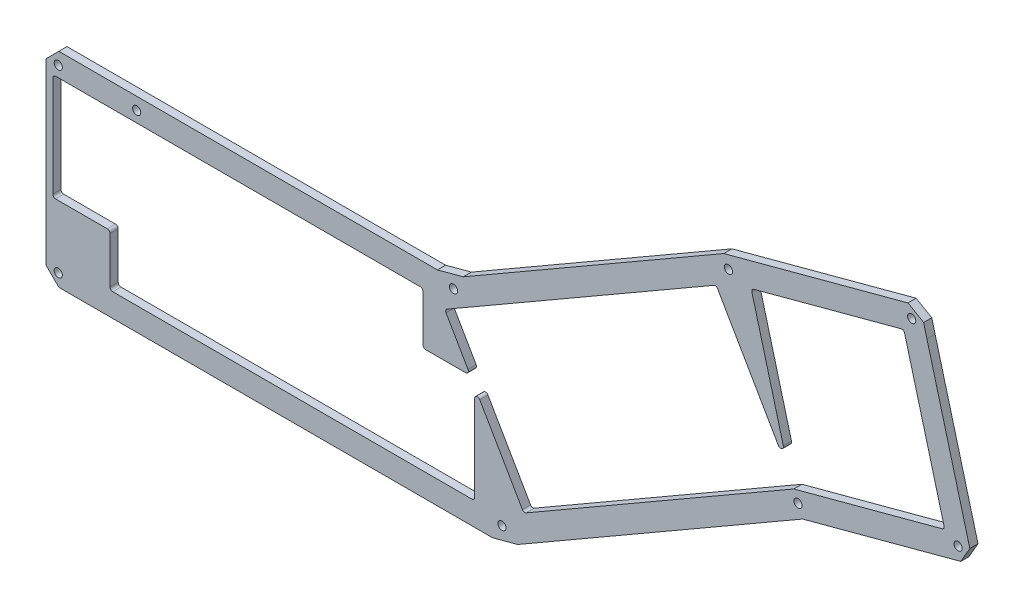
SolidWorks part; units mm, degrees
ref_plane "Plan de face" through (0, 0, 0) normal (0, 0, 1) x (1, 0, 0)
ref_plane "Plan de dessus" through (0, 0, 0) normal (0, 1, 0) x (1, 0, 0)
ref_plane "Plan de droite" through (0, 0, 0) normal (1, 0, 0) x (0, 0, -1)
sketch "Esquisse1" plane through (0, 0, 0) normal (0, 0, 1) x (1, 0, 0)
  line L0 (-73.9886, 18.0851) -> (-59.9886, 18.0851) construction
  line L1 (-73.9886, 37.0851) -> (-59.9886, 37.0851) construction
  line L2 (-73.9886, 37.0851) -> (-73.9886, 23.0851) construction
  line L3 (-73.9886, 23.0851) -> (-59.9886, 23.0851) construction
  line L4 (-59.9886, 37.0851) -> (-59.9886, 23.0851) construction
  line L5 (-73.9886, 18.0851) -> (-73.9886, 4.0851) construction
  line L6 (-73.9886, 4.0851) -> (-59.9886, 4.0851) construction
  line L7 (-59.9886, 18.0851) -> (-59.9886, 4.0851) construction
  line L8 (-73.9886, -0.9149) -> (-59.9886, -0.9149) construction
  line L9 (-73.9886, -0.9149) -> (-73.9886, -14.9149) construction
  line L10 (-73.9886, -14.9149) -> (-59.9886, -14.9149) construction
  line L11 (-59.9886, -0.9149) -> (-59.9886, -14.9149) construction
  line L12 (-73.9886, 37.0851) -> (-73.9886, 18.0851) construction
  line L13 (-54.9886, 18.0851) -> (-40.9886, 18.0851) construction
  line L14 (-54.9886, 37.0851) -> (-40.9886, 37.0851) construction
  line L15 (-54.9886, 37.0851) -> (-54.9886, 23.0851) construction
  line L16 (-54.9886, 23.0851) -> (-40.9886, 23.0851) construction
  line L17 (-40.9886, 37.0851) -> (-40.9886, 23.0851) construction
  line L18 (-54.9886, 18.0851) -> (-54.9886, 4.0851) construction
  line L19 (-54.9886, 4.0851) -> (-40.9886, 4.0851) construction
  line L20 (-40.9886, 18.0851) -> (-40.9886, 4.0851) construction
  line L21 (-54.9886, -0.9149) -> (-40.9886, -0.9149) construction
  line L22 (-54.9886, -0.9149) -> (-54.9886, -14.9149) construction
  line L23 (-54.9886, -14.9149) -> (-40.9886, -14.9149) construction
  line L24 (-40.9886, -0.9149) -> (-40.9886, -14.9149) construction
  line L25 (-54.9886, 37.0851) -> (-54.9886, 18.0851) construction
  line L26 (-35.9886, 18.0851) -> (-21.9886, 18.0851) construction
  line L27 (-35.9886, 37.0851) -> (-21.9886, 37.0851) construction
  line L28 (-35.9886, 37.0851) -> (-35.9886, 23.0851) construction
  line L29 (-35.9886, 23.0851) -> (-21.9886, 23.0851) construction
  line L30 (-21.9886, 37.0851) -> (-21.9886, 23.0851) construction
  line L31 (-35.9886, 18.0851) -> (-35.9886, 4.0851) construction
  line L32 (-35.9886, 4.0851) -> (-21.9886, 4.0851) construction
  line L33 (-21.9886, 18.0851) -> (-21.9886, 4.0851) construction
  line L34 (-35.9886, -0.9149) -> (-21.9886, -0.9149) construction
  line L35 (-35.9886, -0.9149) -> (-35.9886, -14.9149) construction
  line L36 (-35.9886, -14.9149) -> (-21.9886, -14.9149) construction
  line L37 (-21.9886, -0.9149) -> (-21.9886, -14.9149) construction
  line L38 (-35.9886, 37.0851) -> (-35.9886, 18.0851) construction
  line L39 (-16.9886, 18.0851) -> (-2.9886, 18.0851) construction
  line L40 (-16.9886, 37.0851) -> (-2.9886, 37.0851) construction
  line L41 (-16.9886, 37.0851) -> (-16.9886, 23.0851) construction
  line L42 (-16.9886, 23.0851) -> (-2.9886, 23.0851) construction
  line L43 (-2.9886, 37.0851) -> (-2.9886, 23.0851) construction
  line L44 (-16.9886, 18.0851) -> (-16.9886, 4.0851) construction
  line L45 (-16.9886, 4.0851) -> (-2.9886, 4.0851) construction
  line L46 (-2.9886, 18.0851) -> (-2.9886, 4.0851) construction
  line L47 (-16.9886, -0.9149) -> (-2.9886, -0.9149) construction
  line L48 (-16.9886, -0.9149) -> (-16.9886, -14.9149) construction
  line L49 (-16.9886, -14.9149) -> (-2.9886, -14.9149) construction
  line L50 (-2.9886, -0.9149) -> (-2.9886, -14.9149) construction
  line L51 (-16.9886, 37.0851) -> (-16.9886, 18.0851) construction
  line L52 (2.0114, 18.0851) -> (16.0114, 18.0851) construction
  line L53 (2.0114, 37.0851) -> (16.0114, 37.0851) construction
  line L54 (2.0114, 37.0851) -> (2.0114, 23.0851) construction
  line L55 (2.0114, 23.0851) -> (16.0114, 23.0851) construction
  line L56 (16.0114, 37.0851) -> (16.0114, 23.0851) construction
  line L57 (2.0114, 18.0851) -> (2.0114, 4.0851) construction
  line L58 (2.0114, 4.0851) -> (16.0114, 4.0851) construction
  line L59 (16.0114, 18.0851) -> (16.0114, 4.0851) construction
  line L60 (2.0114, -0.9149) -> (16.0114, -0.9149) construction
  line L61 (2.0114, -0.9149) -> (2.0114, -14.9149) construction
  line L62 (2.0114, -14.9149) -> (16.0114, -14.9149) construction
  line L63 (16.0114, -0.9149) -> (16.0114, -14.9149) construction
  line L64 (2.0114, 37.0851) -> (2.0114, 18.0851) construction
  line L65 (21.0114, 18.0851) -> (35.0114, 18.0851) construction
  line L66 (21.0114, 37.0851) -> (35.0114, 37.0851) construction
  line L67 (21.0114, 37.0851) -> (21.0114, 23.0851) construction
  line L68 (21.0114, 23.0851) -> (35.0114, 23.0851) construction
  line L69 (35.0114, 37.0851) -> (35.0114, 23.0851) construction
  line L70 (21.0114, 18.0851) -> (21.0114, 4.0851) construction
  line L71 (21.0114, 4.0851) -> (35.0114, 4.0851) construction
  line L72 (35.0114, 18.0851) -> (35.0114, 4.0851) construction
  line L73 (21.0114, -0.9149) -> (35.0114, -0.9149) construction
  line L74 (21.0114, -0.9149) -> (21.0114, -14.9149) construction
  line L75 (21.0114, -14.9149) -> (35.0114, -14.9149) construction
  line L76 (35.0114, -0.9149) -> (35.0114, -14.9149) construction
  line L77 (21.0114, 37.0851) -> (21.0114, 18.0851) construction
  line L78 (40.0114, 18.0851) -> (54.0114, 18.0851) construction
  line L79 (-97.7538, 39.0851) -> (-97.7538, 2.0851)
  line L80 (-97.7538, 39.0851) -> (-97.7538, 1.0851) construction
  line L81 (-76.7538, 0.0851) -> (-76.7538, -16.9149)
  line L82 (-95.7538, 44.0851) -> (-53.0442, 44.0851) construction
  line L83 (40.0114, 18.0851) -> (40.0114, 4.0851) construction
  line L84 (40.0114, 4.0851) -> (54.0114, 4.0851) construction
  line L85 (54.0114, 18.0851) -> (54.0114, 4.0851) construction
  line L86 (40.0114, -0.9149) -> (54.0114, -0.9149) construction
  line L87 (40.0114, -0.9149) -> (40.0114, -14.9149) construction
  line L88 (40.0114, -14.9149) -> (54.0114, -14.9149) construction
  line L89 (54.0114, -0.9149) -> (54.0114, -14.9149) construction
  line L90 (40.0114, 20.0851) -> (40.0114, 18.0851) construction
  line L91 (-73.9886, 18.0851) -> (-54.9886, 18.0851) construction
  line L92 (56.0114, 20.0851) -> (56.7532, 18.8002) construction
  line L93 (-66.9886, 37.0851) -> (-66.9886, 44.0851) construction
  line L94 (67.3933, 2.371) -> (74.3933, -9.7534) construction
  line L95 (146.1202, 94.012) -> (168.4398, 55.3534)
  line L96 (158.7183, 99.2303) -> (170.2717, 56.1122)
  line L97 (19.0114, 39.0851) -> (37.0114, 39.0851) construction
  line L98 (37.0114, 39.0851) -> (37.0114, 21.0851) construction
  line L99 (19.0114, 21.0851) -> (37.0114, 21.0851) construction
  line L100 (19.0114, 39.0851) -> (19.0114, 21.0851) construction
  line L101 (79.4363, 55.512) -> (88.4363, 39.9235) construction
  line L102 (88.4363, 39.9235) -> (72.8478, 30.9235) construction
  line L103 (63.8478, 46.512) -> (72.8478, 30.9235) construction
  line L104 (79.4363, 55.512) -> (63.8478, 46.512) construction
  line L105 (62.9818, 46.012) -> (71.9818, 30.4235) construction
  line L106 (71.9818, 30.4235) -> (56.3933, 21.4235) construction
  line L107 (47.3933, 37.012) -> (56.3933, 21.4235) construction
  line L108 (62.9818, 46.012) -> (47.3933, 37.012) construction
  line L109 (164.2542, 60.603) -> (148.6657, 51.603) construction
  line L110 (62.2497, 43.2799) -> (71.7497, 26.8254) construction
  line L111 (78.7042, 52.7799) -> (88.2042, 36.3254) construction
  line L112 (95.1587, 62.2799) -> (104.6587, 45.8254) construction
  line L113 (111.6132, 71.7799) -> (121.1132, 55.3254) construction
  line L114 (128.0677, 81.2799) -> (137.5677, 64.8254) construction
  line L115 (144.5221, 90.7799) -> (154.0221, 74.3254) construction
  line L116 (148.6657, 51.603) -> (157.6657, 36.0146) construction
  line L117 (69.1254, 3.371) -> (76.1254, -8.7534) construction
  line L118 (88.2497, -1.7534) -> (76.1254, -8.7534) construction
  line L119 (81.2497, 10.371) -> (88.2497, -1.7534) construction
  line L120 (81.2497, 10.371) -> (69.1254, 3.371) construction
  line L121 (59.6254, 19.8254) -> (66.6254, 7.7011) construction
  line L122 (78.7497, 14.7011) -> (66.6254, 7.7011) construction
  line L123 (71.7497, 26.8254) -> (78.7497, 14.7011) construction
  line L124 (50.1254, 36.2799) -> (57.1254, 24.1556) construction
  line L125 (69.2497, 31.1556) -> (57.1254, 24.1556) construction
  line L126 (62.2497, 43.2799) -> (69.2497, 31.1556) construction
  line L127 (62.2497, 43.2799) -> (50.1254, 36.2799) construction
  line L128 (71.7497, 26.8254) -> (59.6254, 19.8254) construction
  line L129 (85.5799, 12.871) -> (92.5799, 0.7466) construction
  line L130 (104.7042, 7.7466) -> (92.5799, 0.7466) construction
  line L131 (97.7042, 19.871) -> (104.7042, 7.7466) construction
  line L132 (97.7042, 19.871) -> (85.5799, 12.871) construction
  line L133 (76.0799, 29.3254) -> (83.0799, 17.2011) construction
  line L134 (95.2042, 24.2011) -> (83.0799, 17.2011) construction
  line L135 (88.2042, 36.3254) -> (95.2042, 24.2011) construction
  line L136 (66.5799, 45.7799) -> (73.5799, 33.6556) construction
  line L137 (85.7042, 40.6556) -> (73.5799, 33.6556) construction
  line L138 (78.7042, 52.7799) -> (85.7042, 40.6556) construction
  line L139 (78.7042, 52.7799) -> (66.5799, 45.7799) construction
  line L140 (88.2042, 36.3254) -> (76.0799, 29.3254) construction
  line L141 (102.0343, 22.371) -> (109.0343, 10.2466) construction
  line L142 (121.1587, 17.2466) -> (109.0343, 10.2466) construction
  line L143 (114.1587, 29.371) -> (121.1587, 17.2466) construction
  line L144 (114.1587, 29.371) -> (102.0343, 22.371) construction
  line L145 (92.5343, 38.8254) -> (99.5343, 26.7011) construction
  line L146 (111.6587, 33.7011) -> (99.5343, 26.7011) construction
  line L147 (104.6587, 45.8254) -> (111.6587, 33.7011) construction
  line L148 (83.0343, 55.2799) -> (90.0343, 43.1556) construction
  line L149 (102.1587, 50.1556) -> (90.0343, 43.1556) construction
  line L150 (95.1587, 62.2799) -> (102.1587, 50.1556) construction
  line L151 (95.1587, 62.2799) -> (83.0343, 55.2799) construction
  line L152 (104.6587, 45.8254) -> (92.5343, 38.8254) construction
  line L153 (118.4888, 31.871) -> (125.4888, 19.7466) construction
  line L154 (137.6132, 26.7466) -> (125.4888, 19.7466) construction
  line L155 (130.6132, 38.871) -> (137.6132, 26.7466) construction
  line L156 (130.6132, 38.871) -> (118.4888, 31.871) construction
  line L157 (108.9888, 48.3254) -> (115.9888, 36.2011) construction
  line L158 (128.1132, 43.2011) -> (115.9888, 36.2011) construction
  line L159 (121.1132, 55.3254) -> (128.1132, 43.2011) construction
  line L160 (99.4888, 64.7799) -> (106.4888, 52.6556) construction
  line L161 (118.6132, 59.6556) -> (106.4888, 52.6556) construction
  line L162 (111.6132, 71.7799) -> (118.6132, 59.6556) construction
  line L163 (111.6132, 71.7799) -> (99.4888, 64.7799) construction
  line L164 (121.1132, 55.3254) -> (108.9888, 48.3254) construction
  line L165 (134.9433, 41.371) -> (141.9433, 29.2466) construction
  line L166 (154.0677, 36.2466) -> (141.9433, 29.2466) construction
  line L167 (147.0677, 48.371) -> (154.0677, 36.2466) construction
  line L168 (147.0677, 48.371) -> (134.9433, 41.371) construction
  line L169 (125.4433, 57.8254) -> (132.4433, 45.7011) construction
  line L170 (144.5677, 52.7011) -> (132.4433, 45.7011) construction
  line L171 (137.5677, 64.8254) -> (144.5677, 52.7011) construction
  line L172 (115.9433, 74.2799) -> (122.9433, 62.1556) construction
  line L173 (135.0677, 69.1556) -> (122.9433, 62.1556) construction
  line L174 (128.0677, 81.2799) -> (135.0677, 69.1556) construction
  line L175 (128.0677, 81.2799) -> (115.9433, 74.2799) construction
  line L176 (137.5677, 64.8254) -> (125.4433, 57.8254) construction
  line L177 (151.3978, 50.871) -> (158.3978, 38.7466) construction
  line L178 (170.5221, 45.7466) -> (158.3978, 38.7466) construction
  line L179 (163.5221, 57.871) -> (170.5221, 45.7466) construction
  line L180 (163.5221, 57.871) -> (151.3978, 50.871) construction
  line L181 (141.8978, 67.3254) -> (148.8978, 55.2011) construction
  line L182 (161.0221, 62.2011) -> (148.8978, 55.2011) construction
  line L183 (154.0221, 74.3254) -> (161.0221, 62.2011) construction
  line L184 (132.3978, 83.7799) -> (139.3978, 71.6556) construction
  line L185 (151.5221, 78.6556) -> (139.3978, 71.6556) construction
  line L186 (144.5221, 90.7799) -> (151.5221, 78.6556) construction
  line L187 (144.5221, 90.7799) -> (132.3978, 83.7799) construction
  line L188 (154.0221, 74.3254) -> (141.8978, 67.3254) construction
  line L189 (173.2542, 45.0146) -> (157.6657, 36.0146) construction
  line L190 (164.2542, 60.603) -> (173.2542, 45.0146) construction
  line L191 (178.3169, 34.0986) -> (169.0534, 56.4627) construction
  line L192 (169.5193, 62.7839) -> (174.1781, 45.3972) construction
  line L193 (174.1781, 45.3972) -> (191.5647, 50.056) construction
  line L194 (186.906, 67.4426) -> (191.5647, 50.056) construction
  line L195 (162.1337, 98.0749) -> (167.0513, 79.7223) construction
  line L196 (169.5193, 62.7839) -> (186.906, 67.4426) construction
  line L197 (167.0513, 79.7223) -> (180.5742, 83.3457) construction
  line L198 (162.1337, 98.0749) -> (175.6567, 101.6983) construction
  line L199 (162.1337, 98.0749) -> (165.7572, 84.5519) construction
  line L200 (165.7572, 84.5519) -> (179.2801, 88.1754) construction
  line L201 (175.6567, 101.6983) -> (179.2801, 88.1754) construction
  line L202 (167.0513, 79.7223) -> (170.6747, 66.1993) construction
  line L203 (170.6747, 66.1993) -> (184.1977, 69.8228) construction
  line L204 (180.5742, 83.3457) -> (184.1977, 69.8228) construction
  line L205 (171.9688, 61.3697) -> (185.4918, 64.9932) construction
  line L206 (171.9688, 61.3697) -> (175.5923, 47.8467) construction
  line L207 (175.5923, 47.8467) -> (189.1152, 51.4702) construction
  line L208 (185.4918, 64.9932) -> (189.1152, 51.4702) construction
  line L209 (185.4038, 84.6398) -> (198.9268, 88.2633) construction
  line L210 (180.4863, 102.9924) -> (194.0092, 106.6159) construction
  line L211 (180.4863, 102.9924) -> (184.1097, 89.4695) construction
  line L212 (184.1097, 89.4695) -> (197.6327, 93.0929) construction
  line L213 (194.0092, 106.6159) -> (197.6327, 93.0929) construction
  line L214 (185.4038, 84.6398) -> (189.0273, 71.1169) construction
  line L215 (189.0273, 71.1169) -> (202.5503, 74.7403) construction
  line L216 (198.9268, 88.2633) -> (202.5503, 74.7403) construction
  line L217 (190.3214, 66.2873) -> (203.8444, 69.9107) construction
  line L218 (190.3214, 66.2873) -> (193.9449, 52.7643) construction
  line L219 (193.9449, 52.7643) -> (207.4678, 56.3878) construction
  line L220 (203.8444, 69.9107) -> (207.4678, 56.3878) construction
  line L221 (187.8719, 67.7015) -> (192.5307, 50.3148) construction
  line L222 (192.5307, 50.3148) -> (209.9173, 54.9735) construction
  line L223 (205.2586, 72.3602) -> (209.9173, 54.9735) construction
  line L224 (180.4863, 102.9924) -> (185.4038, 84.6398) construction
  line L225 (187.8719, 67.7015) -> (205.2586, 72.3602) construction
  line L226 (203.7564, 89.5574) -> (217.2794, 93.1809) construction
  line L227 (198.8389, 107.91) -> (212.3618, 111.5335) construction
  line L228 (198.8389, 107.91) -> (202.4623, 94.387) construction
  line L229 (202.4623, 94.387) -> (215.9853, 98.0105) construction
  line L230 (212.3618, 111.5335) -> (215.9853, 98.0105) construction
  line L231 (203.7564, 89.5574) -> (207.3799, 76.0344) construction
  line L232 (207.3799, 76.0344) -> (220.9029, 79.6579) construction
  line L233 (217.2794, 93.1809) -> (220.9029, 79.6579) construction
  line L234 (208.674, 71.2048) -> (222.197, 74.8283) construction
  line L235 (208.674, 71.2048) -> (212.2975, 57.6819) construction
  line L236 (212.2975, 57.6819) -> (225.8204, 61.3053) construction
  line L237 (222.197, 74.8283) -> (225.8204, 61.3053) construction
  line L238 (206.2245, 72.619) -> (210.8833, 55.2324) construction
  line L239 (210.8833, 55.2324) -> (228.2699, 59.8911) construction
  line L240 (223.6112, 77.2778) -> (228.2699, 59.8911) construction
  line L241 (198.8389, 107.91) -> (203.7564, 89.5574) construction
  line L242 (206.2245, 72.619) -> (223.6112, 77.2778) construction
  line L243 (167.0513, 79.7223) -> (185.4038, 84.6398) construction
  line L244 (38.0114, 20.0851) -> (56.0114, 20.0851) construction
  line L245 (56.0114, 20.0851) -> (56.0114, 2.0851) construction
  line L246 (38.0114, 2.0851) -> (56.0114, 2.0851) construction
  line L247 (38.0114, 20.0851) -> (38.0114, 2.0851) construction
  line L248 (72.4818, 29.5575) -> (56.8933, 20.5575) construction
  line L249 (56.8933, 20.5575) -> (65.8933, 4.969) construction
  line L250 (81.4818, 13.969) -> (65.8933, 4.969) construction
  line L251 (72.4818, 29.5575) -> (81.4818, 13.969) construction
  line L252 (56.8933, 20.5575) -> (57.6111, 19.3142) construction
  line L253 (164.6018, 81.1365) -> (169.2605, 63.7498) construction
  line L254 (169.2605, 63.7498) -> (186.6472, 68.4086) construction
  line L255 (181.9884, 85.7952) -> (186.6472, 68.4086) construction
  line L256 (164.6018, 81.1365) -> (181.9884, 85.7952) construction
  line L257 (154.7542, 77.0575) -> (163.7542, 61.469) construction
  line L258 (163.7542, 61.469) -> (148.1657, 52.469) construction
  line L259 (139.1657, 68.0575) -> (148.1657, 52.469) construction
  line L260 (154.7542, 77.0575) -> (139.1657, 68.0575) construction
  line L261 (196.3894, 109.3242) -> (213.776, 113.983) construction
  line L262 (-94.7538, 35.7952) -> (-76.7538, 35.7952) construction
  line L263 (-94.7538, 35.7952) -> (-94.7538, 2.7952) construction
  line L264 (-94.7538, 2.7952) -> (-76.7538, 2.7952) construction
  line L265 (-76.7538, 35.7952) -> (-76.7538, 2.7952) construction
  line L266 (213.776, 113.983) -> (218.4348, 96.5963) construction
  line L267 (201.0481, 91.9375) -> (218.4348, 96.5963) construction
  line L268 (196.3894, 109.3242) -> (201.0481, 91.9375) construction
  line L269 (-75.9886, -16.9149) -> (-57.9886, -16.9149) construction
  line L270 (-57.9886, 1.0851) -> (-57.9886, -16.9149) construction
  line L271 (-75.9886, 1.0851) -> (-57.9886, 1.0851) construction
  line L272 (-75.9886, 1.0851) -> (-75.9886, -16.9149) construction
  line L273 (38.0114, -16.9149) -> (56.0114, -16.9149) construction
  line L274 (56.0114, 1.0851) -> (56.0114, -16.9149) construction
  line L275 (38.0114, 1.0851) -> (56.0114, 1.0851) construction
  line L276 (38.0114, 1.0851) -> (38.0114, -16.9149) construction
  line L277 (-75.9886, 39.0851) -> (-57.9886, 39.0851) construction
  line L278 (-57.9886, 39.0851) -> (-57.9886, 21.0851) construction
  line L279 (-75.9886, 21.0851) -> (-57.9886, 21.0851) construction
  line L280 (-75.9886, 39.0851) -> (-75.9886, 21.0851) construction
  line L281 (145.2542, 93.512) -> (129.6657, 84.512) construction
  line L282 (129.6657, 84.512) -> (138.6657, 68.9235) construction
  line L283 (154.2542, 77.9235) -> (138.6657, 68.9235) construction
  line L284 (145.2542, 93.512) -> (154.2542, 77.9235) construction
  line L285 (223.4353, 116.5711) -> (228.0941, 99.1845) construction
  line L286 (148.2159, 106.7689) -> (211.1879, 123.6422) construction
  line L287 (177.5508, 35.9482) -> (235.6877, 51.5259) construction
  line L288 (177.5508, 35.9482) -> (72.9989, -24.4149) construction
  line L289 (-95.7538, -26.9149) -> (63.6687, -26.9149) construction
  line L290 (-100.7538, 35.7952) -> (-100.7538, -21.9149) construction
  line L291 (-75.9886, 49.0851) -> (43.3046, 49.0851) construction
  line L292 (148.2159, 106.7689) -> (52.6347, 51.5851) construction
  line L293 (-75.9886, 49.0851) -> (-57.9886, 49.0851) construction
  line L294 (140.2542, 102.1722) -> (124.6657, 93.1722) construction
  line L295 (193.8012, 118.9835) -> (211.1879, 123.6422) construction
  line L296 (213.4714, 45.5731) -> (230.8581, 50.2318) construction
  line L297 (38.0114, -26.9149) -> (38.0114, -85.4624) construction
  line L298 (178.2542, 36.3543) -> (162.6657, 27.3543) construction
  line L299 (38.0114, -26.9149) -> (56.0114, -26.9149) construction
  line L300 (-100.7538, 2.7952) -> (-100.7538, -38.0419) construction
  line L301 (-100.7538, 35.7952) -> (-100.7538, 2.7952) construction
  line L302 (-75.9886, 49.0851) -> (-95.7538, 49.0851) construction
  line L303 (-100.7538, 44.0851) -> (-100.7538, 35.7952) construction
  line L304 (211.1879, 123.6422) -> (216.0732, 124.9512) construction
  line L305 (222.1691, 121.4083) -> (223.4353, 116.5711) construction
  line L306 (228.0941, 99.1845) -> (239.2233, 57.6497) construction
  line L307 (216.0732, 124.9512) -> (222.1691, 121.4083) construction
  line L308 (235.6877, 51.5259) -> (239.2233, 57.6497) construction
  line L309 (63.6687, -26.9149) -> (72.9989, -24.4149) construction
  line L310 (52.6347, 51.5851) -> (43.3046, 49.0851) construction
  line L311 (-95.7538, 49.0851) -> (-100.7538, 44.0851) construction
  line L312 (-100.7538, -21.9149) -> (-95.7538, -26.9149) construction
  line L313 (-95.7538, 49.0851) -> (-95.7538, 44.0851) construction
  line L314 (-95.7538, 44.0851) -> (-100.7538, 44.0851) construction
  line L315 (-95.7538, -26.9149) -> (-95.7538, -21.9149) construction
  line L316 (68.3338, -25.6649) -> (67.0397, -20.8353) construction
  line L317 (47.9697, 50.3351) -> (49.2637, 45.5055) construction
  line L318 (177.5508, 35.9482) -> (175.6374, 40.5676) construction
  line L319 (148.2159, 106.7689) -> (150.1293, 102.1495) construction
  line L320 (239.2233, 57.6497) -> (234.3936, 56.3556) construction
  line L321 (216.0732, 124.9512) -> (217.3634, 120.1206) construction
  line L322 (146.1202, 94.012) -> (155.1202, 78.4235) construction
  line L323 (-76.7538, 35.7952) -> (-96.7538, 35.7952) construction
  line L324 (148.6019, 105.8371) -> (53.0207, 50.6533) construction
  line L325 (163.6358, 80.8777) -> (168.2946, 63.491) construction
  line L326 (57.0114, 14.621) -> (57.0114, -16.9149)
  line L327 (-77.7538, 1.0851) -> (-96.7538, 1.0851)
  line L328 (-96.7538, 39.0851) -> (-96.7538, 1.0851) construction
  line L329 (53.0207, 50.6533) -> (43.4362, 48.0851) construction
  line L330 (-75.9886, 48.0851) -> (43.4362, 48.0851) construction
  line L331 (-75.9886, 48.0851) -> (-95.3395, 48.0851) construction
  line L332 (-95.3395, 48.0851) -> (-99.7538, 43.6709) construction
  line L333 (-99.7538, 43.6709) -> (-99.7538, 35.7952) construction
  line L334 (-99.7538, 35.7952) -> (-99.7538, -21.5007) construction
  line L335 (-99.7538, -21.5007) -> (-95.3395, -25.9149) construction
  line L336 (-95.3395, -25.9149) -> (63.5371, -25.9149) construction
  line L337 (63.5371, -25.9149) -> (72.6129, -23.483) construction
  line L338 (177.1648, 36.88) -> (72.6129, -23.483) construction
  line L339 (177.1648, 36.88) -> (235.0288, 52.3847) construction
  line L340 (235.0288, 52.3847) -> (238.1501, 57.7909) construction
  line L341 (227.1281, 98.9257) -> (238.1501, 57.7909) construction
  line L342 (222.4686, 116.3151) -> (227.1281, 98.9257) construction
  line L343 (221.307, 120.7527) -> (222.4686, 116.3151) construction
  line L344 (215.9303, 123.8777) -> (221.307, 120.7527) construction
  line L345 (211.4467, 122.6763) -> (215.9303, 123.8777) construction
  line L346 (148.6019, 105.8371) -> (211.4467, 122.6763) construction
  line L347 (214.742, 114.2418) -> (229.2358, 60.1499)
  line L348 (174.0769, 44.3349) -> (228.5287, 58.9252)
  line L349 (174.0769, 44.3349) -> (75.8933, -12.3515)
  line L350 (159.4254, 100.455) -> (213.5172, 114.9489)
  line L351 (144.7542, 94.378) -> (46.8933, 37.878)
  line L352 (-75.7538, -17.9149) -> (56.0114, -17.9149)
  line L353 (-96.7538, 40.0851) -> (37.0114, 40.0851)
  line L354 (2.0114, 40.0851) -> (16.0114, 40.0851) construction
  line L355 (126.5677, 83.878) -> (114.4433, 76.878) construction
  line L356 (179.7098, 105.8902) -> (193.2328, 109.5137) construction
  line L357 (215.2596, 112.3099) -> (218.8831, 98.787) construction
  line L358 (194.7213, 49.8665) -> (208.2443, 53.49) construction
  line L359 (155.5677, 33.6485) -> (143.4433, 26.6485) construction
  line L360 (40.0114, -17.9149) -> (54.0114, -17.9149) construction
  line L361 (58.8774, 15.121) -> (74.5273, -11.9854)
  line L362 (66.5273, 1.871) -> (73.5273, -10.2534) construction
  line L363 (40.0114, 37.0851) -> (40.0114, 23.0851) construction
  line L364 (57.0114, 1.0851) -> (57.0114, -16.9149) construction
  line L365 (46.5273, 36.512) -> (54.568, 22.5851)
  line L366 (51.52, 37.0851) -> (54.0114, 37.0851) construction
  line L367 (40.0114, 23.0851) -> (54.0114, 23.0851) construction
  line L368 (39.0114, 21.0851) -> (53.702, 21.0851)
  line L369 (54.0114, 29.5492) -> (54.0114, 25.5492) construction
  line L370 (38.0114, 39.0851) -> (38.0114, 22.0851)
  line L371 (38.0114, 39.0851) -> (38.0114, 21.0851) construction
  line L372 (46.5273, 36.512) -> (55.5273, 20.9235) construction
  line L373 (-75.9886, 48.5851) -> (43.3704, 48.5851)
  line L374 (38.0114, 21.0851) -> (56.0114, 21.0851) construction
  line L375 (52.8277, 51.1192) -> (43.3704, 48.5851)
  line L376 (148.4089, 106.303) -> (52.8277, 51.1192)
  line L377 (148.4089, 106.303) -> (211.3173, 123.1592)
  line L378 (211.3173, 123.1592) -> (216.0018, 124.4145)
  line L379 (216.0018, 124.4145) -> (221.738, 121.0805)
  line L380 (221.738, 121.0805) -> (222.952, 116.4431)
  line L381 (222.952, 116.4431) -> (227.6111, 99.0551)
  line L382 (227.6111, 99.0551) -> (238.6867, 57.7203)
  line L383 (235.3583, 51.9553) -> (238.6867, 57.7203)
  line L384 (177.3578, 36.4141) -> (235.3583, 51.9553)
  line L385 (177.3578, 36.4141) -> (72.8059, -23.949)
  line L386 (63.6029, -26.4149) -> (72.8059, -23.949)
  line L387 (-95.5467, -26.4149) -> (63.6029, -26.4149)
  line L388 (-100.2538, -21.7078) -> (-95.5467, -26.4149)
  line L389 (-100.2538, 35.7952) -> (-100.2538, -21.7078)
  line L390 (-100.2538, 43.878) -> (-100.2538, 35.7952)
  line L391 (-95.5467, 48.5851) -> (-100.2538, 43.878)
  line L392 (-75.9886, 48.5851) -> (-95.5467, 48.5851)
  circle A0 centre (-95.7538, 44.0851) radius 1.5
  circle A1 centre (-95.7538, -21.9149) radius 1.5
  circle A2 centre (67.0397, -20.8353) radius 1.5
  circle A3 centre (49.2637, 45.5055) radius 1.5
  circle A4 centre (175.6374, 40.5676) radius 1.5
  circle A5 centre (150.1293, 102.1495) radius 1.5
  circle A6 centre (234.3936, 56.3556) radius 1.5
  circle A7 centre (217.3634, 120.1206) radius 1.5
  circle A8 centre (-66.9886, 44.0851) radius 1.5
  arc A9 (168.4398, 55.3534) -> (170.2717, 56.1122) centre (169.3058, 55.8534) ccw
  arc A10 (57.0114, 14.621) -> (58.8774, 15.121) centre (58.0114, 14.621) cw
  arc A11 (53.702, 21.0851) -> (54.568, 22.5851) centre (53.702, 22.0851) ccw
  arc A12 (39.0114, 21.0851) -> (38.0114, 22.0851) centre (39.0114, 22.0851) cw
  arc A13 (-97.7538, 39.0851) -> (-96.7538, 40.0851) centre (-96.7538, 39.0851) cw
  arc A14 (-96.7538, 1.0851) -> (-97.7538, 2.0851) centre (-96.7538, 2.0851) cw
  arc A15 (-76.7538, 0.0851) -> (-77.7538, 1.0851) centre (-77.7538, 0.0851) ccw
  arc A16 (-76.7538, -16.9149) -> (-75.7538, -17.9149) centre (-75.7538, -16.9149) ccw
  arc A17 (228.5287, 58.9252) -> (229.2358, 60.1499) centre (228.2699, 59.8911) ccw
  arc A18 (214.742, 114.2418) -> (213.5172, 114.9489) centre (213.776, 113.983) ccw
  arc A19 (158.7183, 99.2303) -> (159.4254, 100.455) centre (159.6842, 99.4891) cw
  arc A20 (146.1202, 94.012) -> (144.7542, 94.378) centre (145.2542, 93.512) ccw
  arc A21 (57.0114, -16.9149) -> (56.0114, -17.9149) centre (56.0114, -16.9149) cw
  arc A22 (74.5273, -11.9854) -> (75.8933, -12.3515) centre (75.3933, -11.4854) ccw
  arc A23 (46.5273, 36.512) -> (46.8933, 37.878) centre (47.3933, 37.012) cw
  arc A24 (38.0114, 39.0851) -> (37.0114, 40.0851) centre (37.0114, 39.0851) ccw
  point P85 (40.0114, 37.0851)
  point P86 (54.0114, 23.0851)
  point P88 (54.0114, 37.0851)
  point P102 (38.0114, 39.0851)
  point P103 (56.0114, 39.0851)
  point P304 (48.3046, 49.0851)
  point P305 (240.5174, 52.82)
  point P308 (68.6687, -26.9149)
  point P309 (-100.7538, -26.9149)
  point P311 (-100.7538, 49.0851)
  point P312 (220.9029, 126.2453)
  point P409 (172.2377, 48.7752)
  dimension "D32" = 3
  dimension "D33" = 5
  dimension "D40" = 5
  dimension "D41" = 5
  dimension "D42" = 5
  dimension "D43" = 5
  dimension "D44" = 20
  dimension "D53" = 2
  dimension "D56" = 1
  dimension "D59" = 1
  dimension "D63" = 1
  dimension "D64" = 1
  dimension "D65" = 1
  dimension "D1" = 14
  dimension "D2" = 14
  dimension "D4" = 19
  dimension "D6" = 19
  dimension "D7" = 30
  dimension "D10" = 1
  dimension "D11" = 2
  dimension "D13" = 0.5
  dimension "D15" = 2
  dimension "D12" = 7.5
  dimension "D14" = 19
  dimension "D18" = 2
  dimension "D20" = 18
  dimension "D21" = 33
  dimension "D22" = 2
  dimension "D8" = 1
  dimension "D9" = 2
  dimension "D16" = 2
  dimension "D19" = 2
  dimension "D23" = 2
  dimension "D24" = 10
  dimension "D25" = 10
  dimension "D26" = 10
  dimension "D27" = 10
  dimension "D28" = 10
  dimension "D29" = 6
  dimension "D30" = 10
  dimension "D31" = 10
  dimension "D45" = 1
  dimension "D46" = 3
  dimension "D47" = 3
  dimension "D48" = 3
  dimension "D49" = 3
  dimension "D50" = 3
  dimension "D51" = 3
  dimension "D52" = 3
  dimension "D54" = 1
  dimension "D55" = 1
  dimension "D57" = 1
  dimension "D58" = 1
  dimension "D60" = 1
  dimension "D61" = 1
  dimension "D62" = 1
  dimension "D66" = 0.5
  dimension "D3" = 3
  dimension "D5" = 7
  dimension "D17" = 3
extrude "Boss.-Extru.1" add sketch "Esquisse1" along normal blind 3
